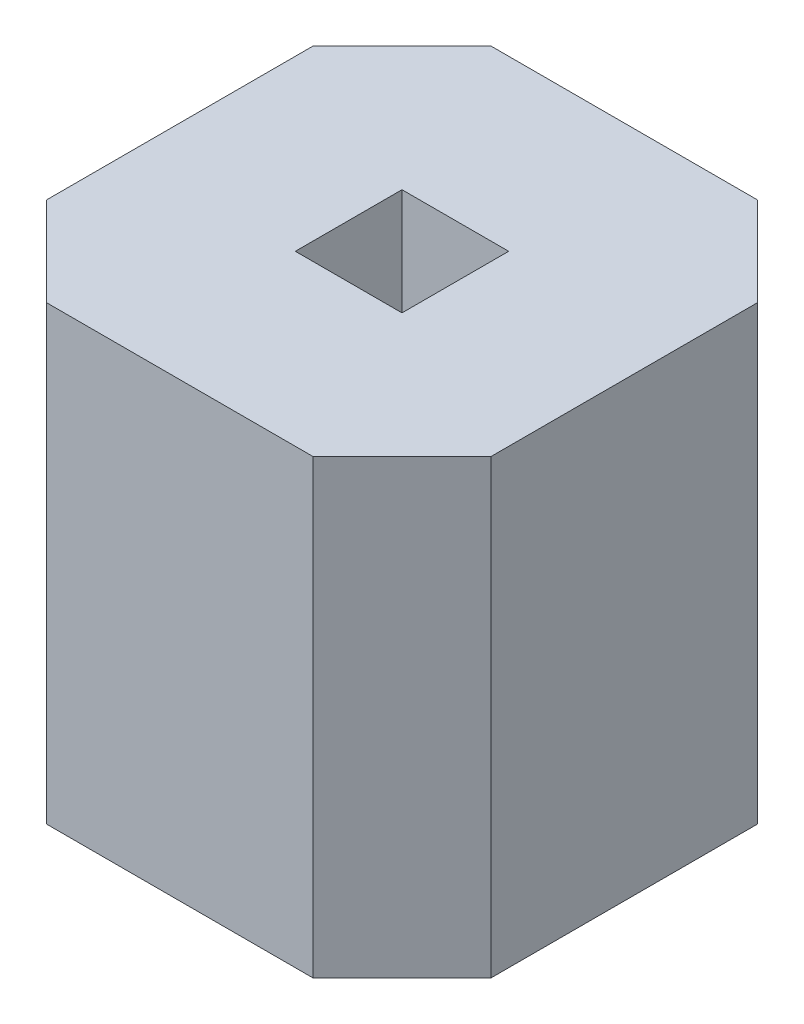
SolidWorks part; units mm, degrees
ref_plane "정면" through (0, 0, 0) normal (0, 0, 1) x (1, 0, 0)
ref_plane "윗면" through (0, 0, 0) normal (0, 1, 0) x (1, 0, 0)
ref_plane "우측면" through (0, 0, 0) normal (1, 0, 0) x (0, 0, -1)
sketch "스케치1" plane through (0, 0, 0) normal (0, 1, 0) x (1, 0, 0)
  line L1 (-1.25, -1.25) -> (1.25, -1.25)
  line L2 (-1.25, -1.25) -> (-1.25, 1.25)
  line L3 (-1.25, 1.25) -> (1.25, 1.25)
  line L4 (1.25, -1.25) -> (1.25, 1.25)
  line L5 (-1.25, -1.25) -> (1.25, 1.25) construction
  line L6 (-1.25, 1.25) -> (1.25, -1.25) construction
  point P0 (0, 0)
  dimension "D1" = 2.5
  dimension "D2" = 2.5
extrude "보스-돌출1" add sketch "스케치1" along normal blind 2.54
chamfer "모따기1" distance 0.5 4 edges at (-1.25, 1.27, 1.25) (-1.25, 1.27, -1.25) (1.25, 1.27, -1.25) (1.25, 1.27, 1.25)
sketch "스케치2" plane through (0, 2.54, 0) normal (0, 1, 0) x (1, 0, 0)
  line L1 (0.3, -0.3) -> (-0.3, -0.3)
  line L2 (0.3, -0.3) -> (0.3, 0.3)
  line L3 (0.3, 0.3) -> (-0.3, 0.3)
  line L4 (-0.3, -0.3) -> (-0.3, 0.3)
  line L5 (0.3, -0.3) -> (-0.3, 0.3) construction
  line L6 (0.3, 0.3) -> (-0.3, -0.3) construction
  point P0 (0, 0)
  dimension "D1" = 0.6
  dimension "D2" = 0.6
extrude "컷-돌출1" cut sketch "스케치2" against normal through all
ref_axis "기준축1" through (0, 2.625, 0) along (0, -1, 0)
